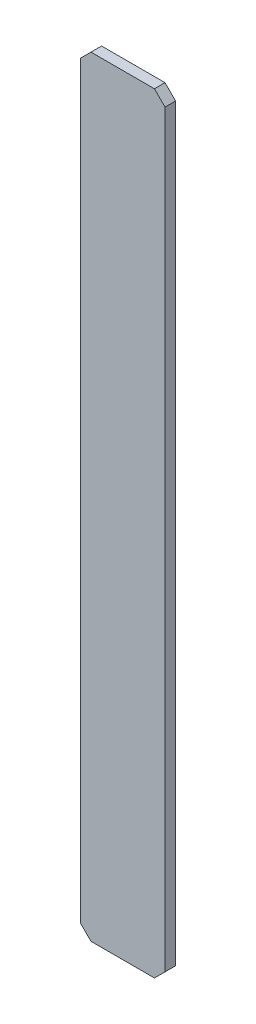
SolidWorks part; units mm, degrees
ref_plane "Front Plane" through (0, 0, 0) normal (0, 0, 1) x (1, 0, 0)
ref_plane "Top Plane" through (0, 0, 0) normal (0, 1, 0) x (1, 0, 0)
ref_plane "Right Plane" through (0, 0, 0) normal (1, 0, 0) x (0, 0, -1)
sketch "Sketch1" plane through (0, 0, 0) normal (0, 1, 0) x (1, 0, 0)
  line L1 (12.7, -1.5875) -> (-12.7, -1.5875)
  line L2 (12.7, -1.5875) -> (12.7, 1.5875)
  line L3 (12.7, 1.5875) -> (-12.7, 1.5875)
  line L4 (-12.7, -1.5875) -> (-12.7, 1.5875)
  line L5 (12.7, -1.5875) -> (-12.7, 1.5875) construction
  line L6 (12.7, 1.5875) -> (-12.7, -1.5875) construction
  point P0 (0, 0)
  dimension "D1" = 12.7
  dimension "D2" = 3.175
extrude "Boss-Extrude1" add sketch "Sketch1" along normal blind 231.14
chamfer "Chamfer1" distance 3.175 angle 45 4 edges at (12.7, 0, 0) (-12.7, 0, 0) (-12.7, 231.14, 0) (12.7, 231.14, 0)
